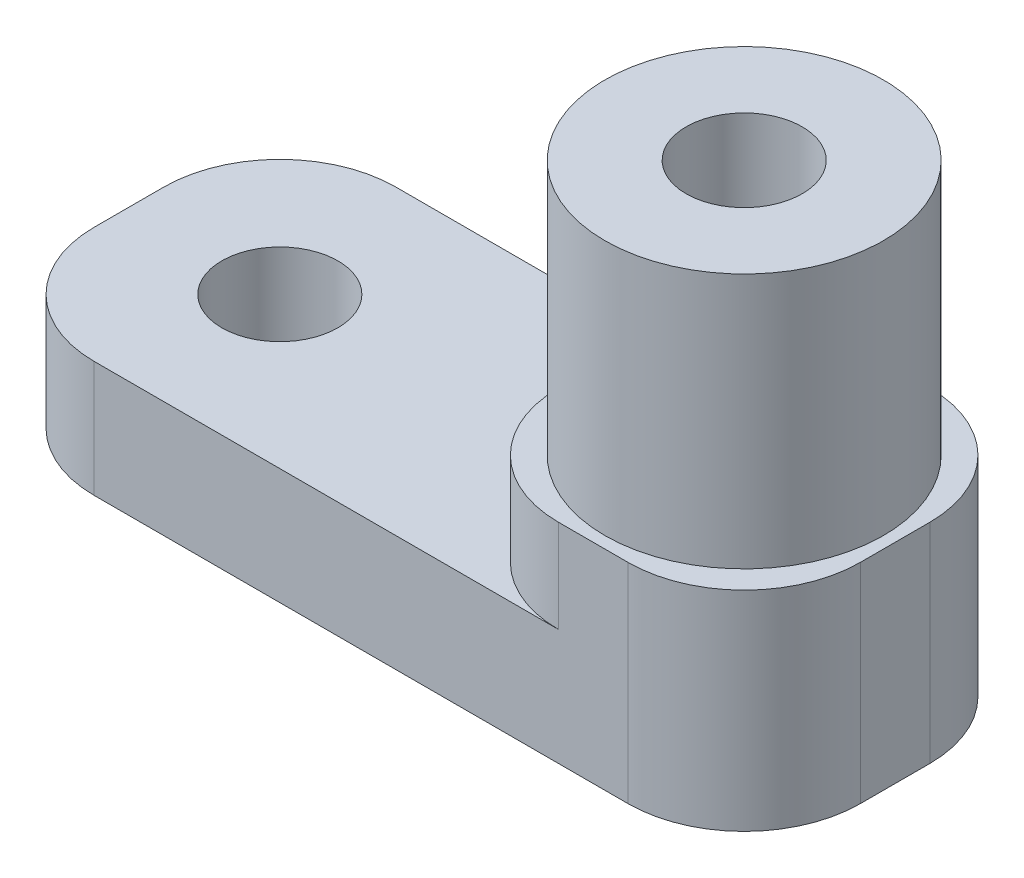
SolidWorks part; units mm, degrees
ref_plane "前视基准面" through (0, 0, 0) normal (0, 0, 1) x (1, 0, 0)
ref_plane "上视基准面" through (0, 0, 0) normal (0, 1, 0) x (1, 0, 0)
ref_plane "右视基准面" through (0, 0, 0) normal (1, 0, 0) x (0, 0, -1)
sketch "草图1" plane through (0, 0, 0) normal (0, 1, 0) x (1, 0, 0)
  line L2 (0, 6) -> (0, -6) construction
  line L4 (-26.5, -6.5) -> (6.5, -6.5)
  line L5 (-26.5, -6.5) -> (-26.5, 6.5)
  line L6 (-26.5, 6.5) -> (6.5, 6.5)
  line L7 (6.5, -6.5) -> (6.5, 6.5)
  line L8 (-26.5, -6.5) -> (6.5, 6.5) construction
  line L9 (-26.5, 6.5) -> (6.5, -6.5) construction
  circle A0 centre (0, 0) radius 6
  circle A1 centre (-20, 0) radius 2.2302
  circle A2 centre (-20, 0) radius 5.85 construction
  point P4 (-10, 0)
  dimension "D1" = 12
  dimension "D3" = 0.5
  dimension "D4" = 10
  dimension "D6" = 11.7
  dimension "D2" = 13
  dimension "D5" = 10
extrude "凸台-拉伸1" add sketch "草图1" along normal blind 5 contours A0 | A0 L2 | L2 A0 region at (-13.2461, 0, 0) region at (0, 0, 0)
extrude "凸台-拉伸2" add sketch "草图1<5>" along normal blind 20 contours L2 A0 | A0 L2 region at (0, 0, 0)
sketch "草图1<5>" plane through (0, 0, 0) normal (0, 1, 0) x (1, 0, 0) same geometry as "草图1"
hole_wizard "M6 螺纹孔1" positions "草图5" profile "草图6" tap size "M6" standard "GB" end condition through all
sketch "草图5" plane through (0, 20, 0) normal (0, 1, 0) x (1, 0, 0)
  point P0 (0, 0)
sketch "草图6" plane through (0, 20, 0) normal (1, 0, 0) x (0, 0, 1)
  line L0 (0, 0) -> (0, 20)
  line L1 (0, 20) -> (2.5, 20)
  line L2 (2.5, 20) -> (2.5, 0)
  line L5 (2.5, 0) -> (0, 0)
  line L11 (0, -6.35) -> (0, 107.95) construction
  dimension "通孔螺纹孔钻头直径" = 5
  dimension "通孔螺纹孔钻头深度" = 20
cosmetic thread "孔螺蚊线1" parameters "D2"=6
hole_wizard "M6 螺纹孔2" positions "草图8" profile "草图9" tap size "M6" standard "GB" end condition through all
sketch "草图8" plane through (0, 5, 0) normal (0, 1, 0) x (1, 0, 0)
  point P0 (-20, 0)
sketch "草图9" plane through (-20, 5, 0) normal (1, 0, 0) x (0, 0, 1)
  line L0 (0, 0) -> (0, 5)
  line L1 (0, 5) -> (2.5, 5)
  line L2 (2.5, 5) -> (2.5, 0)
  line L5 (2.5, 0) -> (0, 0)
  line L11 (0, -6.35) -> (0, 107.95) construction
  dimension "通孔螺纹孔钻头直径" = 5
  dimension "通孔螺纹孔钻头深度" = 5
cosmetic thread "孔螺蚊线2" parameters "D2"=6
sketch "草图10" plane through (0, 5, 0) normal (0, 1, 0) x (1, 0, 0)
  line L0 (-26.5, 6.5) -> (6.5, 6.5) construction
  line L1 (6.5, -6.5) -> (-6.5, -6.5)
  line L2 (6.5, -6.5) -> (6.5, 6.5)
  line L3 (6.5, 6.5) -> (-6.5, 6.5)
  line L4 (-6.5, -6.5) -> (-6.5, 6.5)
  circle A1 centre (0, 0) radius 6
  circle A2 centre (0, 0) radius 6
  dimension "D1" = 13
  dimension "D2" = 0
extrude "凸台-拉伸3" add sketch "草图10" along normal blind 4
sketch "草图11" plane through (0, 0, 0) normal (0, -1, 0) x (1, 0, 0)
  circle A0 centre (-7, 0) radius 3.0809
  dimension "D1" = 7
hole_wizard "M4 螺纹孔1" positions "草图12" profile "草图14" tap size "M4" standard "GB"
sketch "草图12" plane through (0, 0, 0) normal (0, -1, 0) x (-1, 0, 0)
  point P0 (7, 0)
sketch "草图14" plane through (-7, 0, 0) normal (1, 0, 0) x (0, 0, -1)
  line L0 (0, 0) -> (0, 4.9914)
  line L1 (0, 4.9914) -> (1.65, 4)
  line L2 (1.65, 4) -> (1.65, 0)
  line L5 (1.65, 0) -> (0, 0)
  line L10 (0, 4.9914) -> (-1.65, 4) construction
  line L11 (0, -6.35) -> (0, 107.95) construction
  dimension "螺纹孔钻头直径" = 3.3
  dimension "螺纹孔钻头深度" = 4
  dimension "导头角度" = 118
cosmetic thread "孔螺蚊线3" parameters "D1"=4, "D2"=4
fillet "圆角1" radius 5 6 edges at (-6.5, 7, -6.5) (-6.5, 7, 6.5) (6.5, 4.5, 6.5) (6.5, 4.5, -6.5) (-26.5, 2.5, -6.5) (-26.5, 2.5, 6.5)
